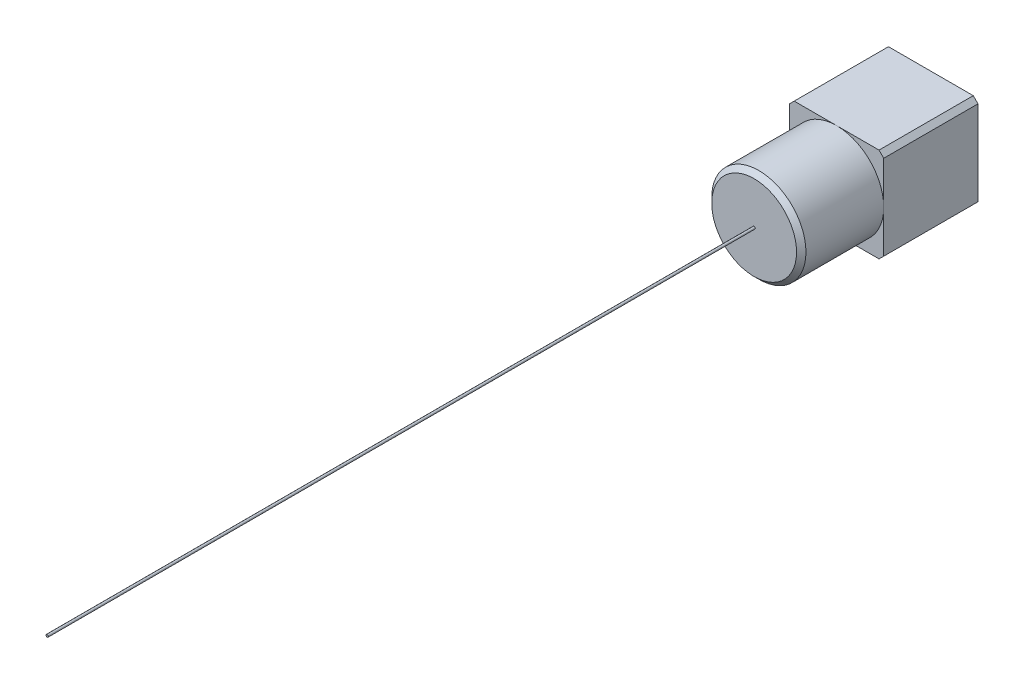
SolidWorks part; units mm, degrees
ref_plane "前视基准面" through (0, 0, 0) normal (0, 0, 1) x (1, 0, 0)
ref_plane "上视基准面" through (0, 0, 0) normal (0, 1, 0) x (1, 0, 0)
ref_plane "右视基准面" through (0, 0, 0) normal (1, 0, 0) x (0, 0, -1)
sketch "草图1" plane through (0, 0, 0) normal (0, 0, 1) x (1, 0, 0)
  line L1 (20, -20) -> (-20, -20)
  line L2 (20, -20) -> (20, 20)
  line L3 (20, 20) -> (-20, 20)
  line L4 (-20, -20) -> (-20, 20)
  line L5 (20, -20) -> (-20, 20) construction
  line L6 (20, 20) -> (-20, -20) construction
  point P0 (0, 0)
  dimension "D1" = 40
  dimension "D2" = 40
extrude "凸台-拉伸1" add sketch "草图1" along normal blind 40
sketch "草图2" plane through (0, 0, 40) normal (0, 0, 1) x (1, 0, 0)
  line L0 (-20, 20) -> (-20, -20) construction
  circle A0 centre (0, 0) radius 20
extrude "凸台-拉伸2" add sketch "草图2" along normal blind 35
ref_axis "基准轴1" through (0, 0, 75) along (0, 0, -1)
sketch "草图8" plane through (0, 0, 0) normal (0, 0, -1) x (-1, 0, 0)
  circle A0 centre (8.6322, 8.0818) radius 3.4392
extrude "凸台-拉伸3" add sketch "草图8" along normal blind 5
fillet "圆角3" radius 0.5 1 edges at (-5.193, 8.0818, 0)
chamfer "倒角1" distance 0.5 angle 45 1 edges at (-12.0714, 8.0818, -5)
chamfer "倒角2" distance 2 angle 45 4 edges at (20, -20, 20) (-20, -20, 20) (20, 20, 20) (-20, 20, 20)
chamfer "倒角3" distance 2 angle 45 1 edges at (20, 0, 75)
sketch "草图9" plane through (0, 0, 75) normal (0, 0, 1) x (1, 0, 0)
  circle A0 centre (0, 0) radius 0.5
  dimension "D1" = 1
extrude "凸台-拉伸4" add sketch "草图9" along normal blind 300
equation "\"29。3\"=10"
